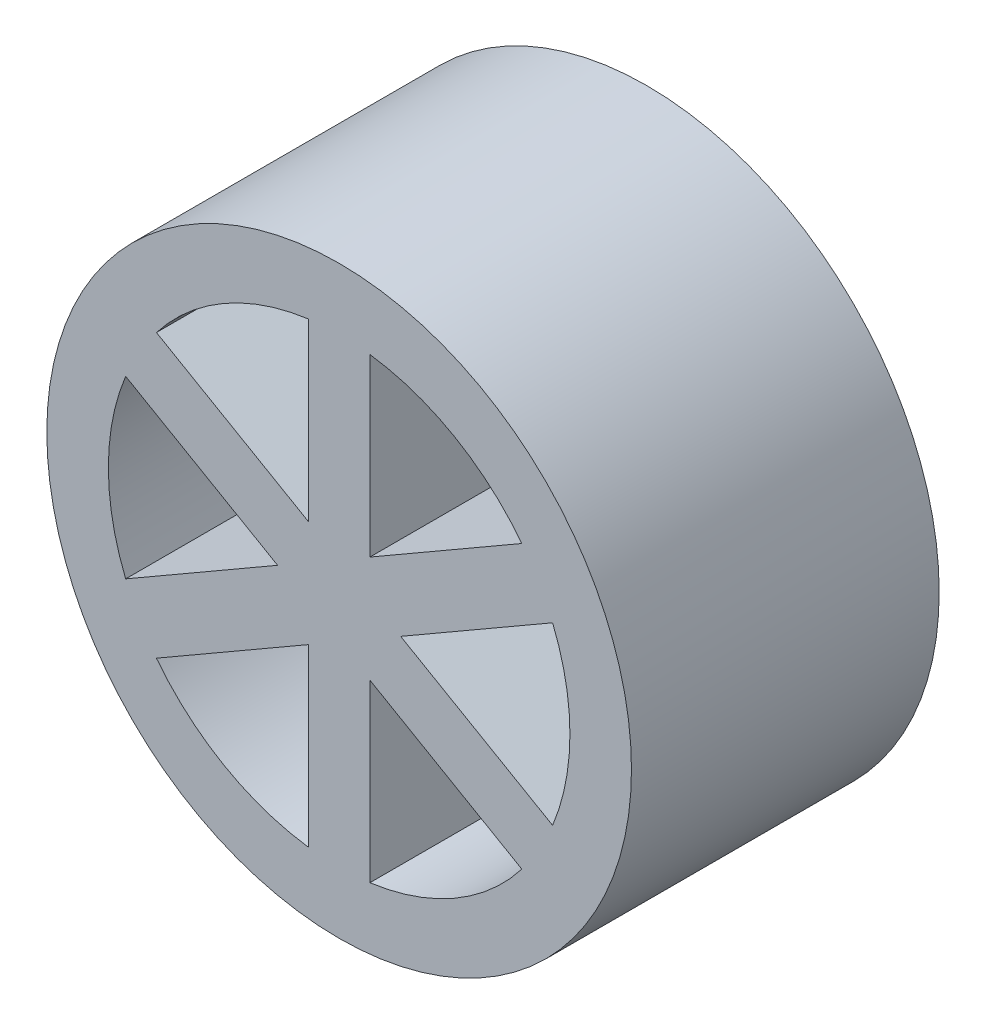
SolidWorks part; units mm, degrees
ref_plane "Płaszczyzna przednia" through (0, 0, 0) normal (0, 0, 1) x (1, 0, 0)
ref_plane "Płaszczyzna górna" through (0, 0, 0) normal (0, 1, 0) x (1, 0, 0)
ref_plane "Płaszczyzna prawa" through (0, 0, 0) normal (1, 0, 0) x (0, 0, -1)
sketch "Szkic1" plane through (0, 0, 0) normal (0, 0, 1) x (1, 0, 0)
  line L0 (-5.9372, -4.5825) -> (-1, -1.7321)
  line L2 (1, -7.433) -> (1, -1.7321)
  line L4 (-1, -7.433) -> (-1, -1.7321)
  line L5 (0.9912, -7.4342) -> (0.2643, -1.9825) construction
  line L6 (0.9912, 7.4342) -> (0.2643, 1.9825) construction
  line L8 (-6.9372, -2.8505) -> (-2, 0)
  line L10 (-6.9372, 2.8505) -> (-2, 0)
  line L12 (-5.9372, 4.5825) -> (-1, 1.7321)
  line L14 (2, 0) -> (6.9372, -2.8505)
  line L15 (-0.2643, -1.9825) -> (-0.9912, -7.4342) construction
  line L19 (-0.2643, 1.9825) -> (-0.9912, 7.4342) construction
  line L21 (1, 1.7321) -> (5.9372, 4.5825)
  line L22 (1, 1.7321) -> (1, 7.433)
  line L23 (2, 0) -> (6.9372, 2.8505)
  line L24 (1, -1.7321) -> (5.9372, -4.5825)
  line L28 (-1, 1.7321) -> (-1, 7.433)
  circle A0 centre (0, 0) radius 2
  circle A1 centre (0, 0) radius 7.5
  circle A2 centre (0, 0) radius 9.5
  point P5 (0, 0)
  point P21 (0, 0)
  dimension "D1" = 4
  dimension "D2" = 15
  dimension "D3" = 2
  dimension "D5" = 3
extrude "Dodanie-wyciągnięcie1" add sketch "Szkic1" along normal blind 10 contours L22 A1 L28 A0 | A0 | L23 A1 L21 A0 | L24 A1 L14 A0 | L4 A1 L2 A0 | L8 A1 L0 A0 | L12 A1 L10 A0 | A2 A1 L21 L23 L14 L24 L2 L4 L0 L8 L10 L12 L28 L22 region at (-4.0659, -2.3475, 0) region at (0, -4.6949, 0) region at (0, 0, 0) region at (-4.0659, 2.3475, 0) region at (4.0659, -2.3475, 0) region at (0, 4.6949, 0) region at (4.0659, 2.3475, 0) region at (-9.2313, 0, 0)
sketch "Szkic2" plane through (0, 0, 0) normal (0, 0, -1) x (-1, 0, 0)
  circle A0 centre (0, 0) radius 2
  dimension "D1" = 4
extrude "Dodanie-wyciągnięcie2" add sketch "Szkic2" along normal blind 5
